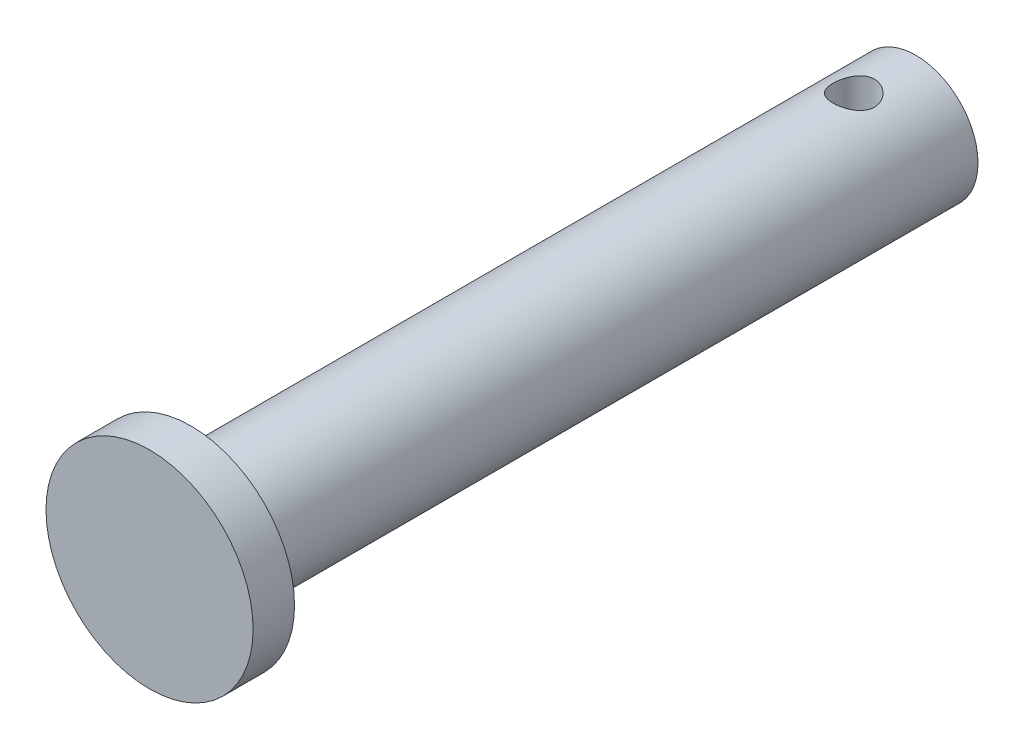
SolidWorks part; units mm, degrees
ref_plane "Front Plane" through (0, 0, 0) normal (0, 0, 1) x (1, 0, 0)
ref_plane "Top Plane" through (0, 0, 0) normal (0, 1, 0) x (1, 0, 0)
ref_plane "Right Plane" through (0, 0, 0) normal (1, 0, 0) x (0, 0, -1)
sketch "Sketch1" plane through (0, 0, 0) normal (0, 0, 1) x (1, 0, 0)
  circle A0 centre (0, 0) radius 3
  dimension "D1" = 6
extrude "Boss-Extrude1" add sketch "Sketch1" along normal blind 35
sketch "Sketch2" plane through (0, 0, 35) normal (0, 0, 1) x (1, 0, 0)
  circle A2 centre (0, 0) radius 5
  circle A3 centre (0, 0) radius 5
  dimension "D1" = 2
extrude "Boss-Extrude2" add sketch "Sketch2" along normal blind 2
sketch "Sketch3" plane through (0, 0, 0) normal (0, 1, 0) x (1, 0, 0)
  line L0 (3, -35) -> (3, 0) construction
  line L1 (3, 0) -> (-3, 0) construction
  circle A0 centre (0, -3) radius 1
  dimension "D1" = 2
  dimension "D2" = 3
  dimension "D3" = 3
extrude "Cut-Extrude1" cut sketch "Sketch3" against normal through all both and the other way through all
sketch "Sketch4" plane through (0, 0, 0) normal (0, 0, -1) x (-1, 0, 0)
  circle A2 centre (0, 0) radius 1.5
  circle A3 centre (0, 0) radius 1.5
  dimension "D1" = 1.5
extrude "Cut-Extrude2" cut sketch "Sketch4" against normal up to surface (35 mm away) up to face at (3, 0, 35)
